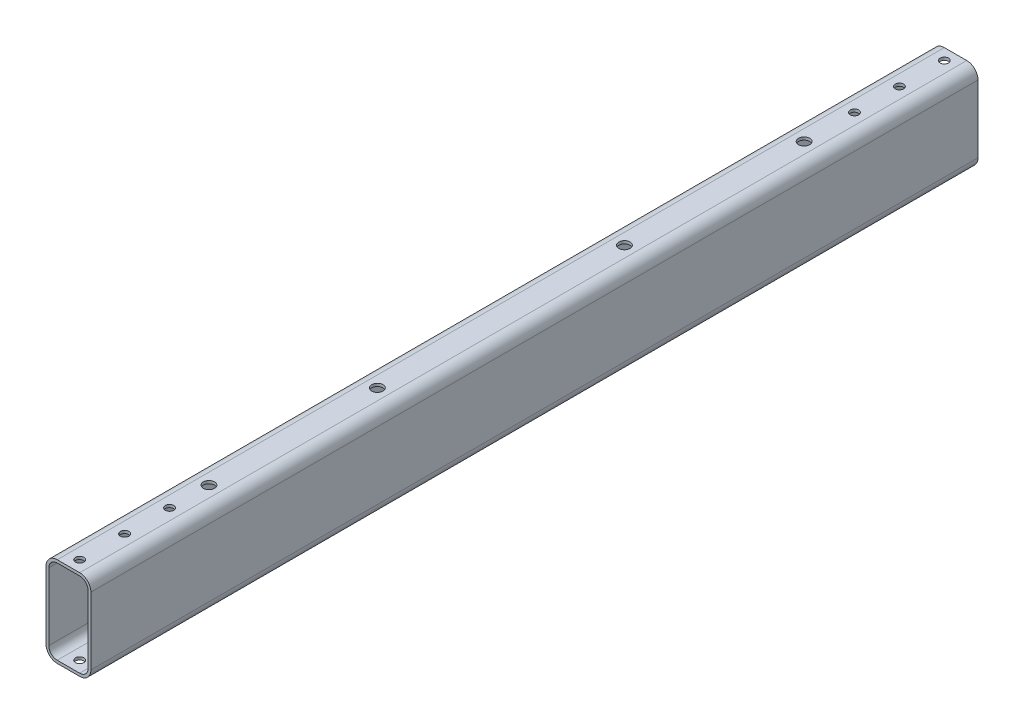
SolidWorks part; units mm, degrees
material "6061-T6 (SS)"
ref_plane "Front Plane" through (0, 0, 0) normal (0, 0, 1) x (1, 0, 0)
ref_plane "Top Plane" through (0, 0, 0) normal (0, 1, 0) x (1, 0, 0)
ref_plane "Right Plane" through (0, 0, 0) normal (1, 0, 0) x (0, 0, -1)
sketch "Sketch1" plane through (0, 0, 0) normal (0, 0, 1) x (1, 0, 0)
  line L1 (-6.35, -25.4) -> (6.35, -25.4)
  line L2 (-12.7, -19.05) -> (-12.7, 19.05)
  line L3 (-6.35, 25.4) -> (6.35, 25.4)
  line L4 (12.7, -19.05) -> (12.7, 19.05)
  line L5 (-12.7, -25.4) -> (12.7, 25.4) construction
  line L6 (-12.7, 25.4) -> (12.7, -25.4) construction
  arc A0 (-12.7, -19.05) -> (-6.35, -25.4) centre (-6.35, -19.05) ccw
  arc A1 (6.35, -25.4) -> (12.7, -19.05) centre (6.35, -19.05) ccw
  arc A2 (6.35, 25.4) -> (12.7, 19.05) centre (6.35, 19.05) cw
  arc A3 (-12.7, 19.05) -> (-6.35, 25.4) centre (-6.35, 19.05) cw
  point P0 (0, 0)
  dimension "D3" = 6.35
  dimension "D1" = 50.8
  dimension "D2" = 25.4
extrude "Extrude-Thin1" add sketch "Sketch1" along normal blind 501.65 thin thin type one direction reverse wall 1.5875
hole_wizard "3/16 (0.1875) Diameter Hole1" positions "3DSketch1" profile "Sketch3" hole size "3/16" standard "ANSI Inch" end condition through all
sketch3d "3DSketch1"
  line L1 (6.35, 25.4, 0) -> (-6.35, 25.4, 0) construction
  line L6 (0, 25.4, 501.65) -> (0, 25.4, 0) construction
  line L7 (6.35, 25.4, 501.65) -> (-6.35, 25.4, 501.65) construction
  point P57 (0, 25.4, 6.35)
  point P59 (0, 25.4, 31.75)
  point P61 (0, 25.4, 57.15)
  point P63 (0, 25.4, 469.9)
  point P65 (0, 25.4, 444.5)
  point P67 (0, 25.4, 495.3)
  dimension "D1" = 25.4
  dimension "D2" = 25.4
  dimension "D3" = 6.35
  dimension "D4" = 25.4
  dimension "D5" = 25.4
  dimension "D6" = 6.35
sketch "Sketch3" plane through (0, 25.4, 495.3) normal (1, 0, 0) x (0, 0, 1)
  line L0 (0, 0) -> (0, 50.8)
  line L1 (0, 50.8) -> (2.3812, 50.8)
  line L2 (2.3812, 50.8) -> (2.3812, 0)
  line L5 (2.3812, 0) -> (0, 0)
  line L11 (0, -6.35) -> (0, 107.95) construction
  dimension "Thru Hole Dia." = 4.7625
  dimension "Thru Hole Depth" = 50.8
hole_wizard "3/16 (0.195) Diameter Hole1" positions "Sketch4" profile "Sketch5" hole size "3/16" standard "ANSI Inch" end condition up to next
sketch "Sketch4" plane through (0, -25.4, 0) normal (0, -1, 0) x (-1, 0, 0)
  point P74 (-3.175, -85.725)
  point P78 (3.175, -111.125)
  point P81 (-3.175, -136.525)
  point P84 (3.175, -161.925)
  point P87 (-3.175, -187.325)
  point P90 (3.175, -212.725)
  point P93 (-3.175, -238.125)
  point P96 (3.175, -263.525)
  point P99 (-3.175, -288.925)
  point P102 (3.175, -314.325)
  point P105 (-3.175, -339.725)
  point P108 (3.175, -365.125)
  point P111 (3.175, -415.925)
  point P114 (-3.175, -390.525)
sketch "Sketch5" plane through (3.175, -25.4, 85.725) normal (1, 0, 0) x (0, 0, -1)
  line L0 (0, 0) -> (0, 1.5875)
  line L1 (0, 1.5875) -> (2.4765, 1.5875)
  line L2 (2.4765, 1.5875) -> (2.4765, 0)
  line L5 (2.4765, 0) -> (0, 0)
  line L11 (0, -6.35) -> (0, 107.95) construction
  dimension "Thru Hole Dia." = 4.953
  dimension "Thru Hole Depth" = 1.5875
hole_wizard "1/4 (0.25) Diameter Hole1" positions "Sketch6" profile "Sketch7" hole size "1/4" standard "ANSI Inch"
sketch "Sketch6" plane through (0, 25.4, 0) normal (0, 1, 0) x (1, 0, 0)
  point P0 (0, -187.2327)
  point P15 (0, -422.2)
  point P23 (0, -326.95)
  point P26 (0, -85.6235)
sketch "Sketch7" plane through (0, 25.4, 187.2327) normal (1, 0, 0) x (0, 0, 1)
  line L0 (0, 0) -> (0, 27.3077)
  line L1 (0, 27.3077) -> (3.175, 25.4)
  line L2 (3.175, 25.4) -> (3.175, 0)
  line L5 (3.175, 0) -> (0, 0)
  line L10 (0, 27.3077) -> (-3.175, 25.4) construction
  line L11 (0, -6.35) -> (0, 107.95) construction
  dimension "Hole Dia." = 6.35
  dimension "Hole Depth" = 25.4
  dimension "Drill Angle" = 118
